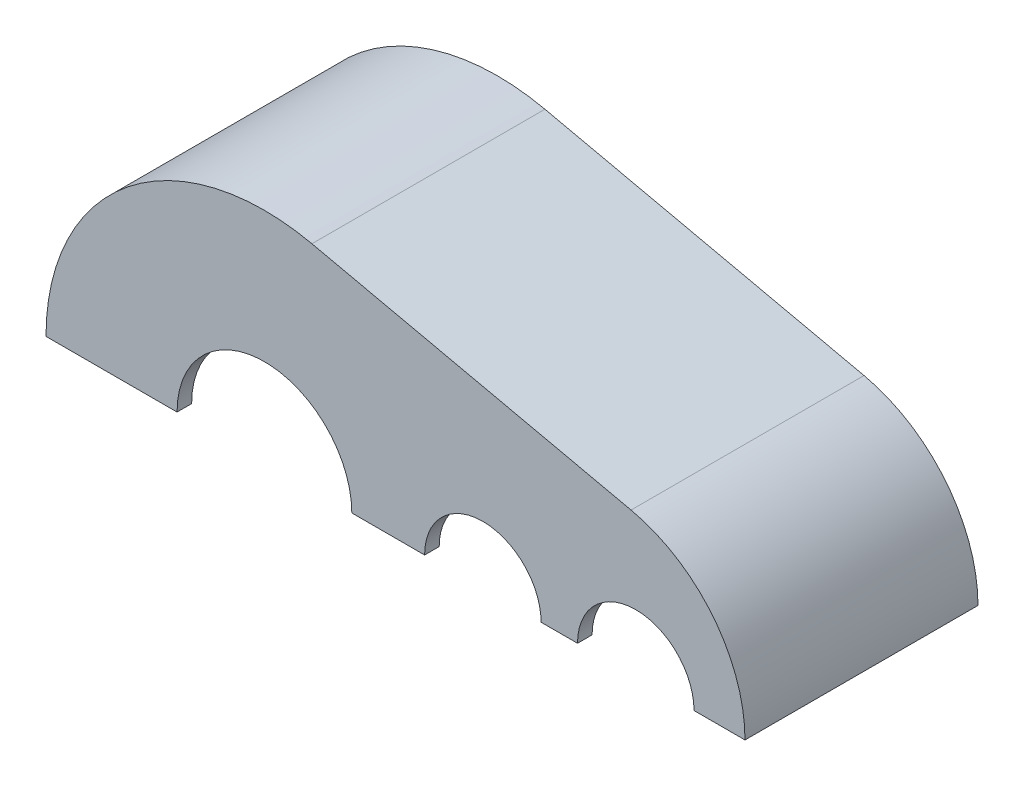
SolidWorks part; units mm, degrees
ref_plane "Front Plane" through (0, 0, 0) normal (0, 0, 1) x (1, 0, 0)
ref_plane "Top Plane" through (0, 0, 0) normal (0, 1, 0) x (1, 0, 0)
ref_plane "Right Plane" through (0, 0, 0) normal (1, 0, 0) x (0, 0, -1)
sketch "Sketch1" plane through (0, 0, 0) normal (0, 1, 0) x (1, 0, 0)
  line L1 (-240, -80) -> (240, -80)
  line L2 (-240, -80) -> (-240, 80)
  line L3 (-240, 80) -> (240, 80)
  line L4 (240, -80) -> (240, 80)
  line L5 (-240, -80) -> (240, 80) construction
  line L6 (-240, 80) -> (240, -80) construction
  point P0 (0, 0)
  dimension "D1" = 480
  dimension "D2" = 160
extrude "Boss-Extrude1" add sketch "Sketch1" along normal blind 150
sketch "Sketch3" plane through (0, 0, 0) normal (0, 0, 1) x (1, 0, 0)
  line L0 (-240, 0) -> (240, 0) construction
  line L2 (-57.3913, 146.4127) -> (161.7391, 97.6085)
  line L3 (-240, 0) -> (240, 0)
  arc A0 (-57.3913, 146.4127) -> (-240, 0) centre (-90, 0) ccw
  arc A1 (240, 0) -> (161.7391, 97.6085) centre (140, 0) ccw
  dimension "D2" = 200
  dimension "D1" = 150
extrude "Cut-Extrude3" cut sketch "Sketch3" against normal through all both and the other way through all flip side to cut
sketch "Sketch5" plane through (0, 0, 0) normal (0, 0, 1) x (1, 0, 0)
  line L0 (-240, 0) -> (240, 0) construction
  circle A0 centre (-90, 0) radius 60
  circle A1 centre (60, 0) radius 40
  circle A2 centre (165, 0) radius 40
  arc A3 (-57.3913, 146.4127) -> (-240, 0) centre (-90, 0) ccw construction
  dimension "D3" = 120
  dimension "D4" = 80
  dimension "D5" = 80
  dimension "D1" = 105
  dimension "D2" = 150
extrude "Cut-Extrude4" cut sketch "Sketch5" against normal through all both and the other way through all
shell "Shell1" thickness 10 removed face at (165, 20, 0) removed face at (60, 20, 0) removed face at (-90, 30, 0) removed face at (222.5, 0, 0) removed face at (112.5, 0, 0) removed face at (-5, 0, 0) removed face at (-195, 0, 0)
sketch "Sketch6" plane through (0, 0, 0) normal (0, 0, 1) x (1, 0, 0)
  line L0 (205, 0) -> (240, 0) construction
  line L1 (100, 0) -> (125, 0) construction
  line L2 (-30, 0) -> (20, 0) construction
  line L3 (-240, 0) -> (-150, 0) construction
  line L4 (205, 0) -> (240, 0)
  line L5 (100, 0) -> (125, 0)
  line L6 (-30, 0) -> (20, 0)
  line L7 (-240, 0) -> (-150, 0)
  line L8 (-150, 0) -> (-280, 0)
  line L9 (205, 0) -> (275, 0)
  arc A0 (205, 0) -> (125, 0) centre (165, 0) ccw construction
  arc A1 (100, 0) -> (20, 0) centre (60, 0) ccw construction
  arc A2 (-30, 0) -> (-150, 0) centre (-90, 0) ccw construction
  arc A3 (205, 0) -> (125, 0) centre (165, 0) ccw
  arc A4 (100, 0) -> (20, 0) centre (60, 0) ccw
  arc A5 (-30, 0) -> (-150, 0) centre (-90, 0) ccw
  dimension "D1" = 130
  dimension "D2" = 70
